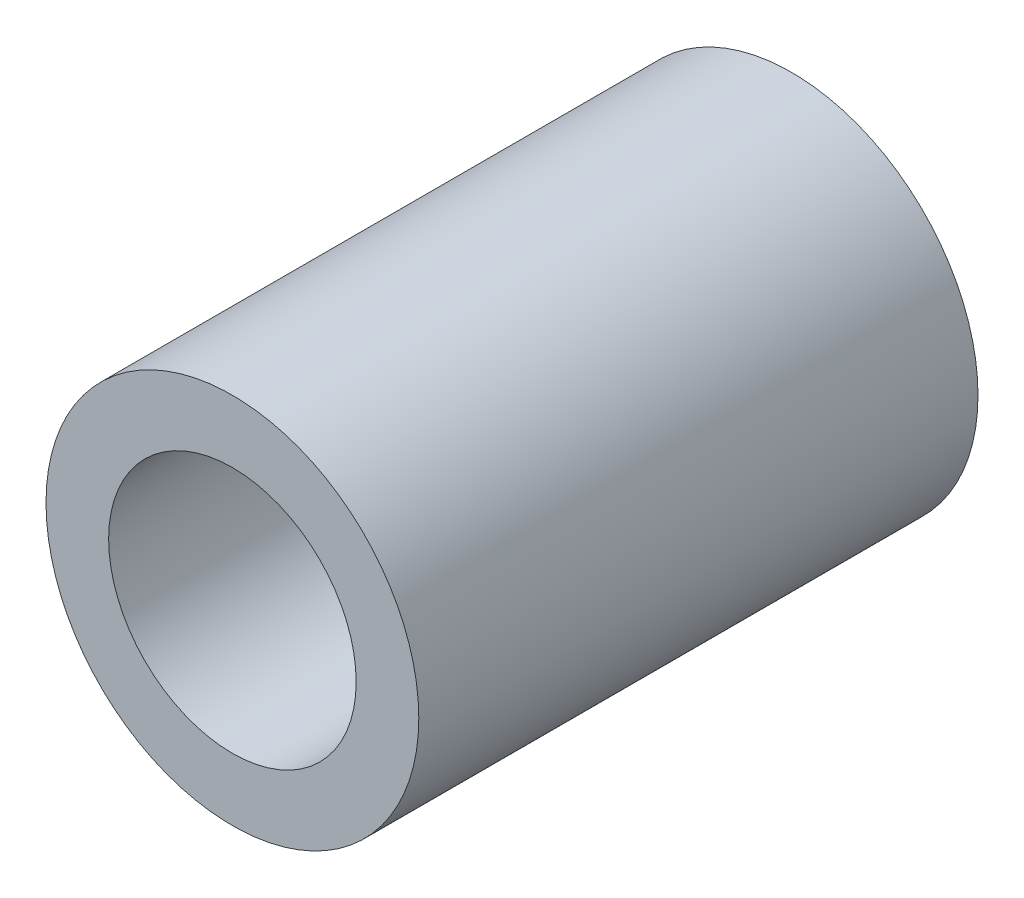
SolidWorks part; units mm, degrees
ref_plane "Front Plane" through (0, 0, 0) normal (0, 0, 1) x (1, 0, 0)
ref_plane "Top Plane" through (0, 0, 0) normal (0, 1, 0) x (1, 0, 0)
ref_plane "Right Plane" through (0, 0, 0) normal (1, 0, 0) x (0, 0, -1)
sketch "Sketch1" plane through (0, 0, 0) normal (0, 0, 1) x (1, 0, 0)
  circle A0 centre (0, 0) radius 3.175
  circle A1 centre (0, 0) radius 2.1082
  dimension "OD" = 6.35
  dimension "ID" = 4.2164
extrude "Extrude1" add sketch "Sketch1" along normal mid plane 9.525
sketch "Sketch2" plane through (0, 0, 0) normal (1, 0, 0) x (0, 0, -1)
  line L0 (-4.7625, -2.1082) -> (4.7625, -2.1082) construction
  line L3 (4.7625, 2.1082) -> (-4.7625, 2.1082) construction
  line L5 (-4.7625, -2.1082) -> (4.7625, -2.1082)
  line L6 (4.7625, 2.1082) -> (-4.7625, 2.1082)
sketch "Sketch4" plane through (0, 0, 4.7625) normal (0, 0, 1) x (1, 0, 0)
  line L0 (0, 0) -> (-1.4907, 1.4907)
  line L1 (0, -1.7463) -> (0, 1.7463) construction
  circle A0 centre (0, 0) radius 2.1082 construction
  dimension "D1" = 45
